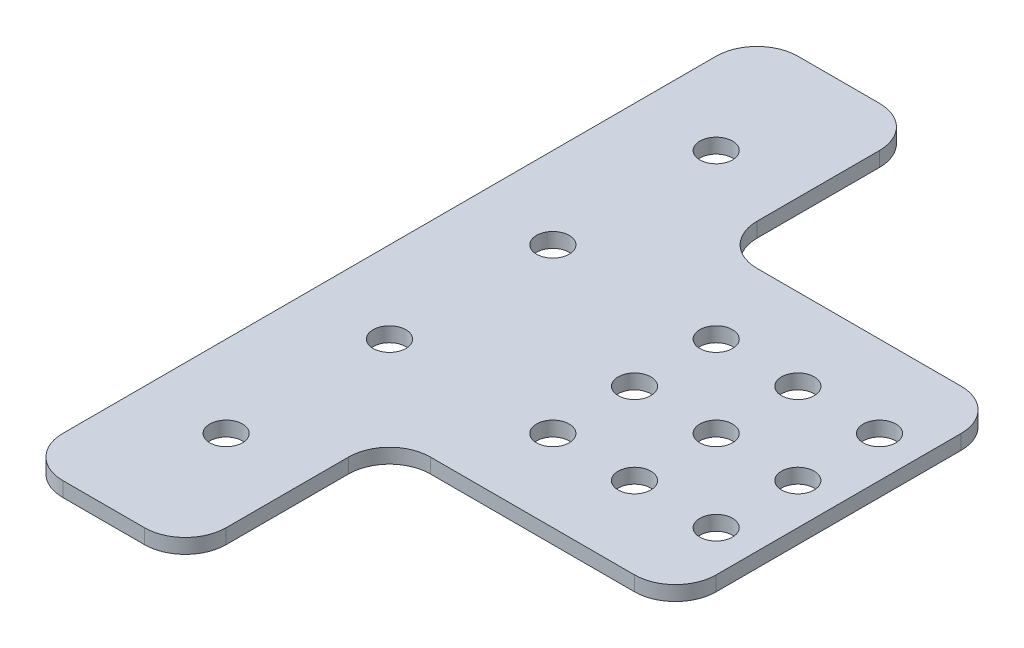
SolidWorks part; units mm, degrees
ref_plane "Front Plane" through (0, 0, 0) normal (0, 0, 1) x (1, 0, 0)
ref_plane "Top Plane" through (0, 0, 0) normal (0, 1, 0) x (1, 0, 0)
ref_plane "Right Plane" through (0, 0, 0) normal (1, 0, 0) x (0, 0, -1)
sketch "Sketch1" plane through (0, 0, 0) normal (0, 1, 0) x (1, 0, 0)
  point P0 (0, 0)
  line B0 (25.4, 114.3) -> (0, 114.3)
  line B1 (0, 114.3) -> (0, 0)
  line B2 (0, 0) -> (25.4, 0)
  line B3 (25.4, 0) -> (25.4, 31.75)
  line B4 (25.4, 31.75) -> (69.85, 31.75)
  line B5 (69.85, 31.75) -> (69.85, 82.55)
  line B6 (69.85, 82.55) -> (25.4, 82.55)
  line B7 (25.4, 82.55) -> (25.4, 114.3)
  circle B8 centre (12.7, 95.25) radius 2.54
  circle B9 centre (12.7, 69.85) radius 2.54
  circle B10 centre (12.7, 44.45) radius 2.54
  circle B11 centre (12.7, 19.05) radius 2.54
  circle B12 centre (38.1, 69.85) radius 2.54
  circle B13 centre (50.8, 69.85) radius 2.54
  circle B14 centre (63.5, 69.85) radius 2.54
  circle B15 centre (50.8, 57.15) radius 2.54
  circle B16 centre (63.5, 57.15) radius 2.54
  circle B17 centre (50.8, 44.45) radius 2.54
  circle B18 centre (63.5, 44.45) radius 2.54
  circle B19 centre (38.1, 57.15) radius 2.54
  circle B20 centre (38.1, 44.45) radius 2.54
sketch_block_instance "Block-2x2_DriveBase_Guessest-1"
sketch_block "Block-2x2_DriveBase_Guessest" parameters "D5"=5.08, "D11"=5.08, "D1"=50.8, "D2"=31.75, "D3"=31.75, "D4"=69.85, "D6"=12.7, "D7"=19.05, "D8"=25.4, "D9"=12.7, "D10"=31.75, "D12"=12.7, "D13"=12.7
extrude "Boss-Extrude1" add sketch "Sketch1" along normal blind 2.286
fillet "Fillet1" radius 6.35 8 edges at (25.4, 1.143, -82.55) (69.85, 1.143, -82.55) (69.85, 1.143, -31.75) (25.4, 1.143, -31.75) (25.4, 1.143, 0) (0, 1.143, -114.3) (25.4, 1.143, -114.3) (0, 1.143, 0)
